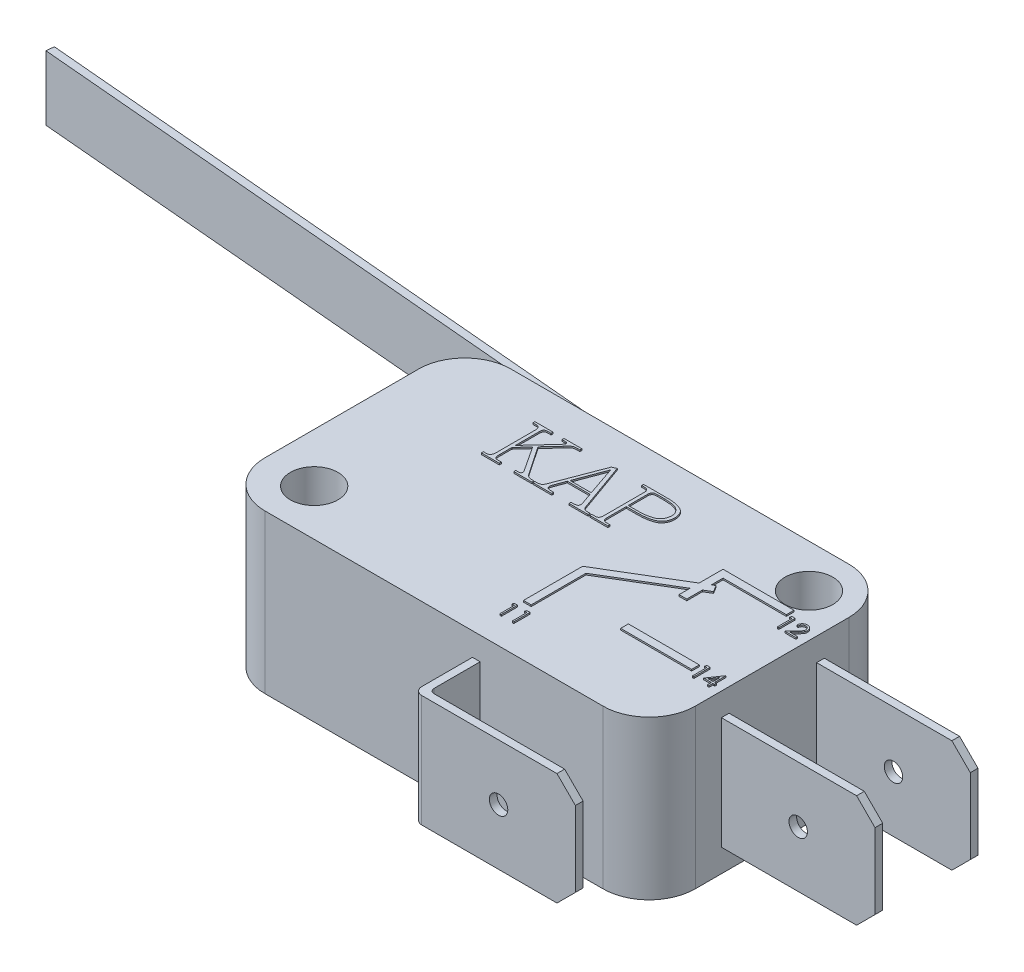
SolidWorks part; units mm, degrees
ref_plane "Plano frontal" through (0, 0, 0) normal (0, 0, 1) x (1, 0, 0)
ref_plane "Plano superior" through (0, 0, 0) normal (0, 1, 0) x (1, 0, 0)
ref_plane "Plano direito" through (0, 0, 0) normal (1, 0, 0) x (0, 0, -1)
sketch "Esboço1" plane through (0, 0, 0) normal (0, 1, 0) x (1, 0, 0)
  line L1 (-68.1435, 2.0444) -> (-40.1435, 2.0444)
  line L2 (-68.1435, 2.0444) -> (-68.1435, -13.9556)
  line L3 (-68.1435, -13.9556) -> (-40.1435, -13.9556)
  line L4 (-40.1435, 2.0444) -> (-40.1435, -13.9556)
extrude "Ressalto-extrusão2" add sketch "Esboço1" along normal blind 10.3
fillet "Filete2" radius 3 1 edges at (-40.1435, 5.15, -2.0444)
fillet "Filete3" radius 3 1 edges at (-40.1435, 5.15, 13.9556)
fillet "Filete4" radius 3 1 edges at (-68.1435, 5.15, -2.0444)
fillet "Filete5" radius 3 1 edges at (-68.1435, 5.15, 13.9556)
sketch "Esboço2" plane through (0, 10.3, 0) normal (0, 1, 0) x (1, 0, 0)
  line L0 (-40.1435, -10.9556) -> (-40.1435, -0.9556) construction
  line L1 (-43.1435, 2.0444) -> (-65.1435, 2.0444) construction
  circle A0 centre (-64.9435, -10.9556) radius 1.55
  circle A1 centre (-42.9435, -0.7556) radius 1.55
  dimension "D1" = 3.1
  dimension "D2" = 3.1
  dimension "D4" = 2.8
  dimension "D5" = 22
  dimension "D6" = 10.2
  dimension "D3" = 2.8
extrude "Corte-extrusão1" cut sketch "Esboço2" against normal blind 10.3
sketch "Esboço3" plane through (-40.1435, 0, 0) normal (1, 0, 0) x (0, 0, -1)
  line L0 (-10.9556, 10.3) -> (-0.9556, 10.3) construction
  line L1 (-2.5556, 8.8) -> (-3.0556, 8.8)
  line L2 (-2.5556, 8.8) -> (-2.5556, 1.5)
  line L3 (-2.5556, 1.5) -> (-3.0556, 1.5)
  line L4 (-3.0556, 8.8) -> (-3.0556, 1.5)
  line L5 (-10.9556, 0) -> (-0.9556, 0) construction
  line L6 (-0.9556, 0) -> (-0.9556, 10.3) construction
  line L8 (-8.7556, 8.8) -> (-9.2556, 8.8)
  line L9 (-8.7556, 8.8) -> (-8.7556, 1.5)
  line L10 (-8.7556, 1.5) -> (-9.2556, 1.5)
  line L11 (-9.2556, 8.8) -> (-9.2556, 1.5)
  line L13 (-10.9556, 10.3) -> (-10.9556, 0) construction
  dimension "D1" = 1.5
  dimension "D2" = 1.5
  dimension "D3" = 1.6
  dimension "D4" = 0.5
  dimension "D5" = 0.5
  dimension "D6" = 5.7
  dimension "D7" = 1.7
extrude "Ressalto-extrusão3" add sketch "Esboço3" along normal blind 10
sketch "Esboço4" plane through (0, 0, 13.9556) normal (0, 0, 1) x (1, 0, 0)
  line L0 (-65.1435, 10.3) -> (-43.1435, 10.3) construction
  line L1 (-51.6435, 8.8) -> (-51.1435, 8.8)
  line L2 (-51.6435, 8.8) -> (-51.6435, 1.5)
  line L3 (-51.6435, 1.5) -> (-51.1435, 1.5)
  line L4 (-51.1435, 8.8) -> (-51.1435, 1.5)
  line L5 (-65.1435, 0) -> (-43.1435, 0) construction
  line L6 (-43.1435, 0) -> (-43.1435, 10.3) construction
  dimension "D1" = 0.5
  dimension "D2" = 1.5
  dimension "D3" = 1.5
  dimension "D4" = 8
extrude "Ressalto-extrusão4" add sketch "Esboço4" along normal blind 3.8
sketch "Esboço5" plane through (-51.1435, 0, 0) normal (1, 0, 0) x (0, 0, -1)
  line L0 (-17.7556, 1.5) -> (-13.9556, 1.5) construction
  line L1 (-17.7556, 8.8) -> (-17.2556, 8.8)
  line L2 (-17.7556, 8.8) -> (-17.7556, 1.5)
  line L3 (-17.7556, 1.5) -> (-17.2556, 1.5)
  line L4 (-17.2556, 8.8) -> (-17.2556, 1.5)
  dimension "D1" = 0.5
extrude "Ressalto-extrusão5" add sketch "Esboço5" along normal blind 10
fillet "Filete8" radius 0.5 1 edges at (-51.6435, 5.15, 17.7556)
fillet "Filete9" radius 0.3 1 edges at (-51.1435, 5.15, 17.2556)
sketch "Esboço6" plane through (0, 0, -2.0444) normal (0, 0, -1) x (-1, 0, 0)
  line L1 (51.4435, 3.05) -> (50.9435, 3.05)
  line L2 (51.4435, 3.05) -> (51.4435, 7.25)
  line L3 (51.4435, 7.25) -> (50.9435, 7.25)
  line L4 (50.9435, 3.05) -> (50.9435, 7.25)
  line L6 (43.1435, 10.3) -> (43.1435, 0) construction
  line L7 (51.4435, 5.15) -> (65.1435, 5.15) construction
  line L8 (65.1435, 0) -> (65.1435, 10.3) construction
  dimension "D1" = 4.2
  dimension "D3" = 0.5
  dimension "D4" = 7.8
extrude "Ressalto-extrusão6" add sketch "Esboço6" along normal blind 2
sketch "Esboço10" plane through (0, 0, -2.0444) normal (0, 0, -1) x (-1, 0, 0)
  line L0 (62.9134, 5.15) -> (65.1435, 5.15) construction
  line L1 (62.9134, 2.9) -> (60.0481, 2.9)
  line L2 (62.9134, 2.9) -> (62.9134, 7.4)
  line L3 (62.9134, 7.4) -> (60.0481, 7.4)
  line L4 (60.0481, 2.9) -> (60.0481, 7.4)
  line L5 (65.1435, 0) -> (65.1435, 10.3) construction
  dimension "D1" = 4.5
extrude "Ressalto-extrusão7" add sketch "Esboço10" along normal blind 1.9
fillet "Filete11" radius 0.6 2 edges at (-60.0481, 5.15, -3.9444) (-62.9134, 5.15, -3.9444)
chamfer "Chanfro1" distance 0.5 angle 5 1 edges at (-51.4435, 5.15, -4.0444) first distance on face at (-51.4435, 5.15, -3.0444)
sketch "Esboço12" plane through (-51.3604, 0, -4.4935) normal (-0.9962, 0, -0.0872) x (-0.0872, 0, 0.9962)
  line L1 (0.4507, 3.05) -> (0.9527, 3.05)
  line L2 (0.4507, 3.05) -> (0.4507, 7.25)
  line L3 (0.4507, 7.25) -> (0.9527, 7.25)
  line L4 (0.9527, 3.05) -> (0.9527, 7.25)
extrude "Ressalto-extrusão8" add sketch "Esboço12" along normal blind 50
chamfer "Chanfro2" distance 1.2 angle 45 6 edges at (-41.1435, 8.8, 17.5056) (-41.1435, 1.5, 17.5056) (-30.1435, 8.8, 9.0056) (-30.1435, 8.8, 2.8056) (-30.1435, 1.5, 9.0056) (-30.1435, 1.5, 2.8056)
sketch "Esboço13" plane through (0, 0, 2.5556) normal (0, 0, -1) x (-1, 0, 0)
  line L0 (30.1435, 5.15) -> (40.1435, 5.15) construction
  line L1 (30.1435, 2.7) -> (30.1435, 7.6) construction
  line L2 (40.1435, 1.5) -> (40.1435, 8.8) construction
  circle A0 centre (35.1435, 5.15) radius 0.6
  dimension "D1" = 1.2
  dimension "D2" = 5
extrude "Corte-extrusão2" cut sketch "Esboço13" against normal blind 10
sketch "Esboço14" plane through (0, 0, 17.7556) normal (0, 0, 1) x (1, 0, 0)
  line L0 (-41.1435, 5.15) -> (-51.1435, 5.15) construction
  line L1 (-41.1435, 7.6) -> (-41.1435, 2.7) construction
  line L2 (-51.1435, 8.8) -> (-51.1435, 1.5) construction
  circle A0 centre (-46.1435, 5.15) radius 0.6
  dimension "D1" = 1.2
extrude "Corte-extrusão3" cut sketch "Esboço14" against normal up to next
sketch "Esboço15" plane through (0, 10.3, 0) normal (0, 1, 0) x (1, 0, 0)
  text T0 "KAP\r\n" font "@Adobe Ming Std L" height 3.5
extrude "Ressalto-extrusão9" add sketch "Esboço15" along normal blind 0.1
sketch "Esboço16" plane through (0, 0, 0) normal (0, -1, 0) x (1, 0, 0)
  text T0 "MV7"
extrude "Corte-extrusão4" cut sketch "Esboço16" against normal blind 0.1
sketch "Esboço17" plane through (0, 0, 0) normal (0, -1, 0) x (1, 0, 0)
  text T0 "15A 250VAC\r\n15(3A) 250~\r\nT85" font "Century Gothic" height in points 5
extrude "Corte-extrusão5" cut sketch "Esboço17" against normal blind 0.1
sketch "Esboço18" plane through (0, 10.3, 0) normal (0, 1, 0) x (1, 0, 0)
  line L0 (-46.8547, -5.2963) -> (-46.8547, -4.5807)
  line L1 (-46.8547, -2.4369) -> (-42.2356, -2.4369)
  line L2 (-42.2356, -9.0985) -> (-46.8547, -9.0985)
  line L3 (-51.5907, -10.6853) -> (-51.5907, -6.8392)
  line L4 (-51.5907, -6.8392) -> (-46.8547, -3.9976)
  line L5 (-51.0907, -10.6853) -> (-51.0907, -7.1223)
  line L6 (-51.0907, -7.1223) -> (-46.8547, -4.5807)
  line L7 (-42.2356, -8.5985) -> (-46.8547, -8.5985)
  line L8 (-46.3547, -5.2963) -> (-46.3547, -4.2807)
  line L9 (-46.3547, -2.9369) -> (-42.2356, -2.9369)
  line L10 (-42.2356, -2.4369) -> (-42.2356, -2.9369)
  line L11 (-42.2356, -8.5985) -> (-42.2356, -9.0985)
  line L12 (-46.8547, -8.5985) -> (-46.8547, -9.0985)
  line L13 (-46.8547, -5.2963) -> (-46.3547, -5.2963)
  line L14 (-46.1609, -3.5813) -> (-45.9036, -4.0101)
  line L15 (-51.5907, -10.6853) -> (-51.0907, -10.6853)
  line L16 (-46.3547, -4.2807) -> (-45.9036, -4.0101)
  line L17 (-46.3547, -3.6976) -> (-46.1609, -3.5813)
  line L18 (-51.0907, -7.1223) -> (-45.9036, -4.0101) construction
  line L19 (-46.8547, -3.9976) -> (-46.8547, -2.4369)
  line L20 (-51.5907, -6.8392) -> (-46.1609, -3.5813) construction
  line L21 (-46.3547, -3.6976) -> (-46.3547, -2.9369)
  line L22 (-46.8547, -5.2963) -> (-46.8547, -2.4369) construction
  line L24 (-46.3547, -5.2963) -> (-46.3547, -2.9369) construction
  dimension "D1" = 0.5
  dimension "D2" = 0.5
extrude "Ressalto-extrusão10" add sketch "Esboço18" along normal blind 0.1
sketch "Esboço20" plane through (0, 10.3, 0) normal (0, 1, 0) x (1, 0, 0)
  text T0 "                         12\r\n\r\n                         14\r\n 11\r\n" font "Century Gothic" height in points 4
extrude "Ressalto-extrusão11" add sketch "Esboço20" along normal blind 0.1
